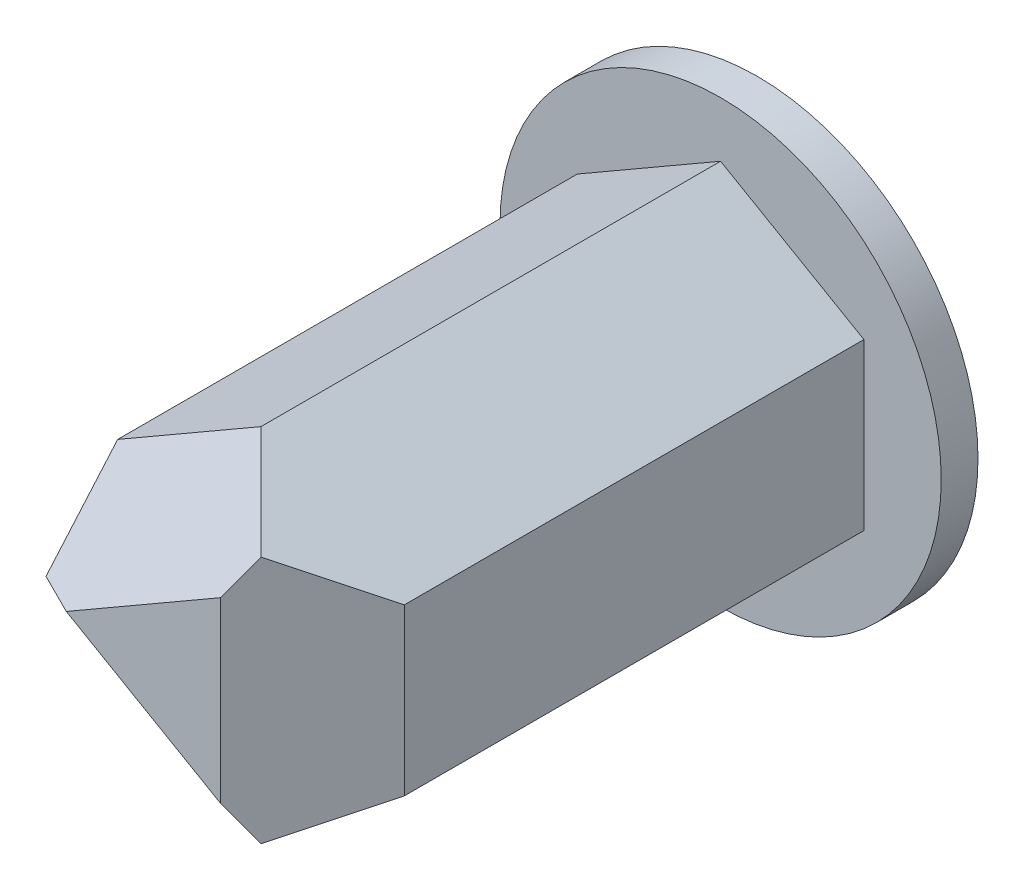
SolidWorks part; units mm, degrees
ref_plane "Alzado" through (0, 0, 0) normal (0, 0, 1) x (1, 0, 0)
ref_plane "Planta" through (0, 0, 0) normal (0, 1, 0) x (1, 0, 0)
ref_plane "Vista lateral" through (0, 0, 0) normal (1, 0, 0) x (0, 0, -1)
sketch "Croquis1" plane through (0, 0, 0) normal (0, 0, 1) x (1, 0, 0)
  line L1 (0, 9) -> (-7.7942, 4.5)
  line L2 (-7.7942, 4.5) -> (-7.7942, -4.5)
  line L3 (-7.7942, -4.5) -> (0, -9)
  line L4 (0, -9) -> (7.7942, -4.5)
  line L5 (7.7942, -4.5) -> (7.7942, 4.5)
  line L6 (7.7942, 4.5) -> (0, 9)
  circle A0 centre (0, 0) radius 7.7942 construction
  dimension "D1" = 9
extrude "Saliente-Extruir1" add sketch "Croquis1" along normal blind 30
sketch "Croquis2" plane through (0, 0, 0) normal (0, 0, -1) x (-1, 0, 0)
  circle A0 centre (0, 0) radius 12
  dimension "D1" = 24
extrude "Saliente-Extruir2" add sketch "Croquis2" along normal blind 2
chamfer "Chamfer1" distance 5 angle 45 3 edges at (7.7942, 0, 30) (-3.8971, 6.75, 30) (-3.8971, -6.75, 30)
